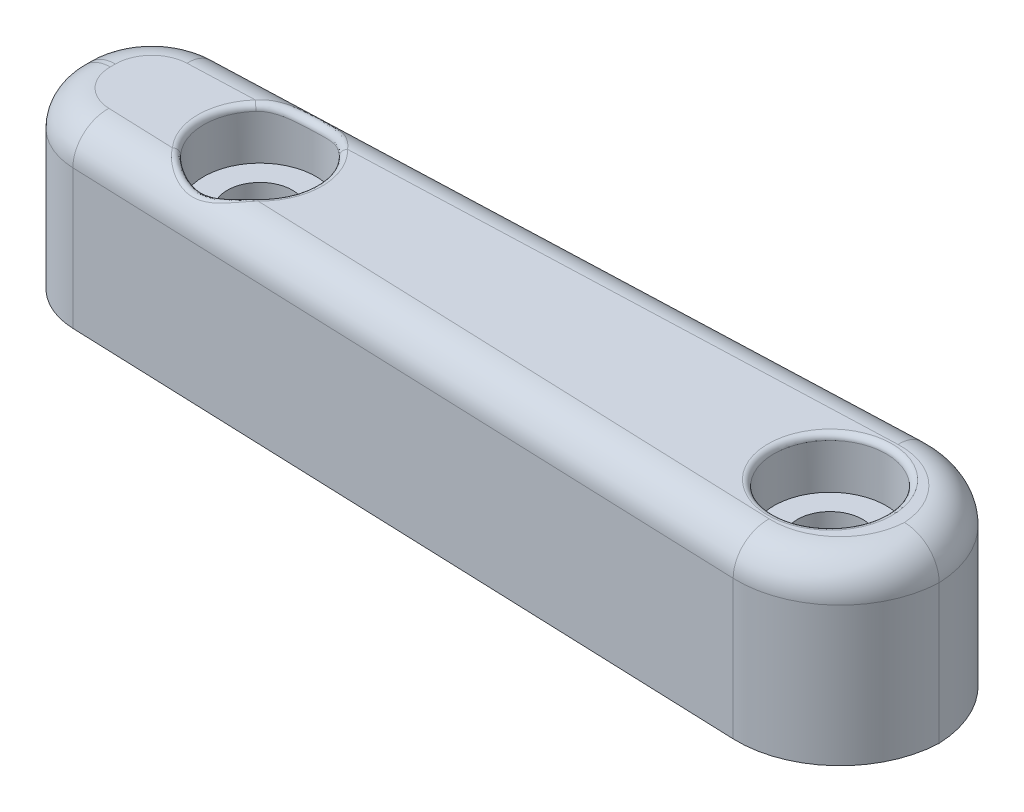
SolidWorks part; units mm, degrees
ref_plane "Front Plane" through (0, 0, 0) normal (0, 0, 1) x (1, 0, 0)
ref_plane "Top Plane" through (0, 0, 0) normal (0, 1, 0) x (1, 0, 0)
ref_plane "Right Plane" through (0, 0, 0) normal (1, 0, 0) x (0, 0, -1)
sketch "Sketch1" plane through (0, 0, 0) normal (0, 1, 0) x (1, 0, 0)
  line L1 (0, 0) -> (188.7833, -6.985)
  line L2 (0, 0) -> (0, 31.242)
  line L3 (0, 31.242) -> (188.7833, 38.227)
  line L4 (188.7833, -6.985) -> (188.7833, 38.227)
  line L5 (0, 15.621) -> (188.7833, 15.621) construction
  circle A0 centre (39.878, 15.621) radius 7.1437
  circle A1 centre (164.846, 15.621) radius 7.1438
  dimension "D4" = 14.2875
  dimension "D6" = 14.2875
  dimension "D1" = 188.9125
  dimension "D2" = 45.212
  dimension "D5" = 31.242
  dimension "D3" = 39.878
  dimension "D7" = 124.968
extrude "Boss-Extrude1" add sketch "Sketch1" along normal blind 38.1
fillet "Fillet1" radius 15.621 2 edges at (0, 19.05, 0) (0, 19.05, -31.242)
fillet "Fillet3" radius 22.606 2 edges at (188.7833, 19.05, 6.985) (188.7833, 19.05, -38.227)
fillet "Fillet4" radius 7.62 7 edges at (0, 38.1, -15.621) (4.3729, 38.1, -4.2141) (90.1924, 38.1, 3.3371) (181.5543, 38.1, 0.0975) (181.5543, 38.1, -31.3395) (90.1924, 38.1, -34.5791) (4.3729, 38.1, -27.0279)
sketch "Sketch2" plane through (0, 38.1, 0) normal (0, 1, 0) x (1, 0, 0)
  circle A0 centre (39.878, 15.621) radius 12.319
  circle A1 centre (164.846, 15.621) radius 12.319
  dimension "D1" = 24.638
  dimension "D2" = 24.638
extrude "Cut-Extrude1" cut sketch "Sketch2" against normal blind 11.1125
fillet "Fillet5" radius 1.27 1 edges at (164.846, 38.1, -3.302)
fillet "Fillet6" radius 1.27 4 edges at (40.3347, 37.5588, -3.3105) (27.559, 38.1, -15.621) (38.5128, 37.5588, -27.8641) (52.197, 38.1, -15.621)
equation "\"D6@Sketch1\"=\"D4@Sketch1\""
equation "\"D2@Sketch2\"=\"D1@Sketch2\""
